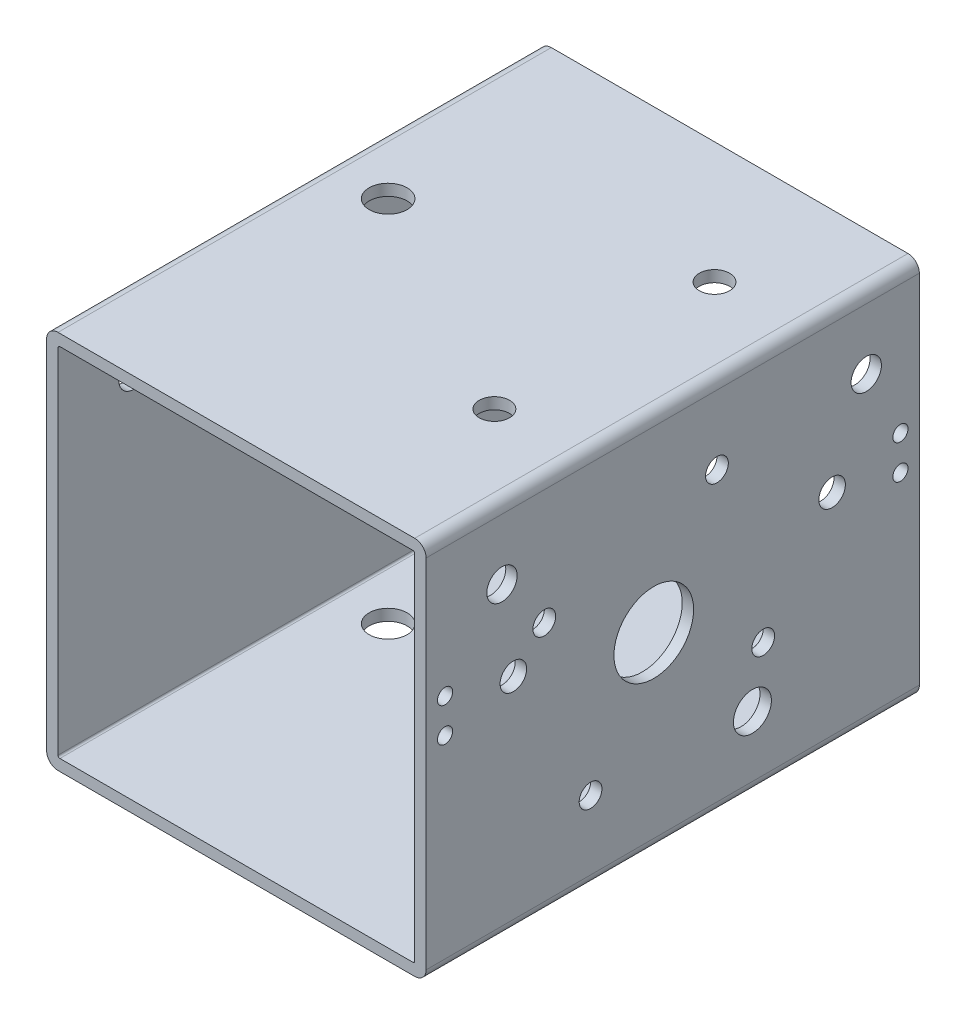
SolidWorks part; units mm, degrees
ref_plane "Front Plane" through (0, 0, 0) normal (0, 0, 1) x (1, 0, 0)
ref_plane "Top Plane" through (0, 0, 0) normal (0, 1, 0) x (1, 0, 0)
ref_plane "Right Plane" through (0, 0, 0) normal (1, 0, 0) x (0, 0, -1)
sketch "Sketch1" plane through (0, 0, 0) normal (0, 0, 1) x (1, 0, 0)
  line L1 (-50, 50) -> (50, 50)
  line L2 (-50, 50) -> (-50, -50)
  line L3 (-50, -50) -> (50, -50)
  line L4 (50, 50) -> (50, -50)
  line L5 (-50, 50) -> (50, -50) construction
  line L6 (-50, -50) -> (50, 50) construction
  point P0 (0, 0)
  dimension "D1" = 100
  dimension "D2" = 100
extrude "Extrude-Thin1" add sketch "Sketch1" along normal blind 130 thin thin type one direction reverse wall 3
fillet "Fillet1" radius 0.5 4 edges at (-47, -47, 65) (-47, 47, 65) (47, 47, 65) (47, -47, 65)
fillet "Fillet2" radius 3 4 edges at (50, -50, 65) (-50, -50, 65) (50, 50, 65) (-50, 50, 65)
sketch "Holes - top" plane through (0, 0, 0) normal (0, 1, 0) x (1, 0, 0)
  line L0 (-3, 0) -> (-3, -130) construction
  line L1 (47, -130) -> (-47, -130) construction
  line L2 (-23, 0) -> (-23, -130) construction
  line L3 (47, 0) -> (-47, 0) construction
  line L4 (17, 0) -> (17, -130) construction
  circle A0 centre (-34, -56) radius 11 construction
  circle A1 centre (28, -90) radius 11 construction
  circle A2 centre (28, -32) radius 11 construction
  dimension "D4" = 22
  dimension "D1" = 40
  dimension "D2" = 40
  dimension "D3" = 32
  dimension "D5" = 56
  dimension "D6" = 3
hole_wizard "Ø8.0 (8) Diameter Hole2" positions "Sketch6" profile "Sketch5" hole size "Ø8.0" standard "ANSI Metric" end condition through all
sketch "Sketch6" plane through (0, 50, 0) normal (0, 1, 0) x (1, 0, 0)
  point P0 (28, -32)
  point P6 (28, -90)
sketch "Sketch5" plane through (28, 50, 32) normal (1, 0, 0) x (0, 0, 1)
  line L0 (0, 0) -> (0, 100)
  line L1 (0, 100) -> (4, 100)
  line L2 (4, 100) -> (4, 0)
  line L5 (4, 0) -> (0, 0)
  line L11 (0, -6.35) -> (0, 107.95) construction
  dimension "Thru Hole Dia." = 8
  dimension "Thru Hole Depth" = 100
sketch "Holes - side" plane through (0, 0, 0) normal (1, 0, 0) x (0, 0, -1)
  line L0 (0, 0) -> (-130, 0) construction
  line L1 (-130, -47) -> (-130, 47) construction
  line L2 (-130, 20) -> (0, 20) construction
  line L3 (0, -47) -> (0, 47) construction
  line L4 (-130, -20) -> (0, -20) construction
  circle A0 centre (-110, 31) radius 11 construction
  circle A1 centre (-14, 31) radius 11 construction
  circle A2 centre (-44, -31) radius 11 construction
  dimension "D1" = 40
  dimension "D2" = 22
  dimension "D3" = 20
  dimension "D4" = 14
  dimension "D5" = 44
hole_wizard "Ø8.0 (8) Diameter Hole3" positions "Sketch9" profile "Sketch8" hole size "Ø8.0" standard "ANSI Metric" end condition through all
sketch "Sketch9" plane through (50, 0, 0) normal (1, 0, 0) x (0, 0, -1)
  point P0 (-14, 31)
  point P3 (-110, 31)
sketch "Sketch8" plane through (50, 31, 14) normal (0, 1, 0) x (0, 0, -1)
  line L0 (0, 0) -> (0, 100)
  line L1 (0, 100) -> (4, 100)
  line L2 (4, 100) -> (4, 0)
  line L5 (4, 0) -> (0, 0)
  line L11 (0, -6.35) -> (0, 107.95) construction
  dimension "Thru Hole Dia." = 8
  dimension "Thru Hole Depth" = 100
hole_wizard "Ø10.0 (10) Diameter Hole1" positions "Sketch12" profile "Sketch11" hole size "Ø10.0" standard "ANSI Metric" end condition through all
sketch "Sketch12" plane through (0, 50, 0) normal (0, 1, 0) x (1, 0, 0)
  point P0 (-34, -56)
sketch "Sketch11" plane through (-34, 50, 56) normal (1, 0, 0) x (0, 0, 1)
  line L0 (0, 0) -> (0, 100)
  line L1 (0, 100) -> (5, 100)
  line L2 (5, 100) -> (5, 0)
  line L5 (5, 0) -> (0, 0)
  line L11 (0, -6.35) -> (0, 107.95) construction
  dimension "Thru Hole Dia." = 10
  dimension "Thru Hole Depth" = 100
hole_wizard "Ø10.0 (10) Diameter Hole2" positions "Sketch14" profile "Sketch13" hole size "Ø10.0" standard "ANSI Metric" end condition through all
sketch "Sketch14" plane through (50, 0, 0) normal (1, 0, 0) x (0, 0, -1)
  point P0 (-44, -31)
sketch "Sketch13" plane through (50, -31, 44) normal (0, 1, 0) x (0, 0, -1)
  line L0 (0, 0) -> (0, 100)
  line L1 (0, 100) -> (5, 100)
  line L2 (5, 100) -> (5, 0)
  line L5 (5, 0) -> (0, 0)
  line L11 (0, -6.35) -> (0, 107.95) construction
  dimension "Thru Hole Dia." = 10
  dimension "Thru Hole Depth" = 100
hole_wizard "M8x1.25 Tapped Hole1" positions "Sketch18" profile "Sketch17" tap size "M8x1.25" standard "ANSI Metric" end condition up to next
sketch "Sketch18" plane through (-50, 0, 0) normal (-1, 0, 0) x (0, 0, 1)
  line L0 (56, 35) -> (56, -15) construction
  point P0 (56, -15)
  point P2 (56, 35)
  dimension "D1" = 56
  dimension "D2" = 35
  dimension "D3" = 15
sketch "Sketch17" plane through (-50, -15, 56) normal (0, 1, 0) x (0, 0, 1)
  line L0 (0, 0) -> (0, 3)
  line L1 (0, 3) -> (3.4, 3)
  line L2 (3.4, 3) -> (3.4, 0)
  line L5 (3.4, 0) -> (0, 0)
  line L11 (0, -6.35) -> (0, 107.95) construction
  dimension "Thru Tap Drill Dia." = 6.8
  dimension "Thru Tap Drill Depth" = 3
cosmetic thread "Hole Thread1" parameters "D2"=8
cosmetic thread "Hole Thread2" parameters "D2"=8
hole_wizard "M8x1.25 Tapped Hole2" positions "Sketch21" profile "Sketch20" tap size "M8x1.25" standard "ANSI Metric" end condition up to next
sketch "Sketch21" plane through (0, -50, 0) normal (0, -1, 0) x (-1, 0, 0)
  line L0 (20, -44) -> (-35, -44) construction
  point P0 (20, -44)
  point P2 (-35, -44)
  dimension "D1" = 44
  dimension "D2" = 35
  dimension "D3" = 20
sketch "Sketch20" plane through (-20, -50, 44) normal (1, 0, 0) x (0, 0, -1)
  line L0 (0, 0) -> (0, 3)
  line L1 (0, 3) -> (3.4, 3)
  line L2 (3.4, 3) -> (3.4, 0)
  line L5 (3.4, 0) -> (0, 0)
  line L11 (0, -6.35) -> (0, 107.95) construction
  dimension "Thru Tap Drill Dia." = 6.8
  dimension "Thru Tap Drill Depth" = 3
cosmetic thread "Hole Thread3" parameters "D2"=8
cosmetic thread "Hole Thread4" parameters "D2"=8
sketch "Holes - Nema 23 motor" plane through (0, 0, 0) normal (1, 0, 0) x (0, 0, -1)
  line L0 (-98.8427, 16.6524) -> (-53.3476, 28.8427) construction
  line L1 (-98.8427, 16.6524) -> (-86.6524, -28.8427) construction
  line L2 (-53.3476, 28.8427) -> (-41.1573, -16.6524) construction
  line L3 (-86.6524, -28.8427) -> (-41.1573, -16.6524) construction
  line L4 (-98.8427, 16.6524) -> (-41.1573, -16.6524) construction
  line L5 (-53.3476, 28.8427) -> (-86.6524, -28.8427) construction
  line L6 (0, 0) -> (-130, 0) construction
  point P1 (-70, 0)
  dimension "D1" = 70
  dimension "D2" = 47.1
  dimension "D3" = 47.1
  dimension "D4" = 15
hole_wizard "Ø21.0 (21) Diameter Hole1" positions "Sketch24" profile "Sketch23" hole size "Ø21.0" standard "ANSI Metric" end condition up to next
sketch "Sketch24" plane through (50, 0, 0) normal (1, 0, 0) x (0, 0, -1)
  point P0 (-70, 0)
sketch "Sketch23" plane through (50, 0, 70) normal (0, 1, 0) x (0, 0, -1)
  line L0 (0, 0) -> (0, 3)
  line L1 (0, 3) -> (10.5, 3)
  line L2 (10.5, 3) -> (10.5, 0)
  line L5 (10.5, 0) -> (0, 0)
  line L11 (0, -6.35) -> (0, 107.95) construction
  dimension "Thru Hole Dia." = 21
  dimension "Thru Hole Depth" = 3
hole_wizard "Ø6.0 (6) Diameter Hole1" positions "Sketch26" profile "Sketch25" hole size "Ø6.0" standard "ANSI Metric" end condition up to next
sketch "Sketch26" plane through (50, 0, 0) normal (1, 0, 0) x (0, 0, -1)
  point P0 (-41.1573, -16.6524)
  point P3 (-53.3476, 28.8427)
  point P6 (-98.8427, 16.6524)
  point P9 (-86.6524, -28.8427)
sketch "Sketch25" plane through (50, -16.6524, 41.1573) normal (0, 1, 0) x (0, 0, -1)
  line L0 (0, 0) -> (0, 3)
  line L1 (0, 3) -> (3, 3)
  line L2 (3, 3) -> (3, 0)
  line L5 (3, 0) -> (0, 0)
  line L11 (0, -6.35) -> (0, 107.95) construction
  dimension "Thru Hole Dia." = 6
  dimension "Thru Hole Depth" = 3
sketch "Sketch27" plane through (50, 0, 0) normal (1, 0, 0) x (0, 0, -1)
  line L1 (0, -47) -> (0, 47) construction
  line L2 (-130, 50) -> (0, 50) construction
  line L3 (-65, 66.9997) -> (-65, -40.3101) construction
  line L4 (-130, -47) -> (-130, 47) construction
  circle A0 centre (-5, 13) radius 2
  circle A1 centre (-5, 4) radius 2
  circle A2 centre (-23, 8.5) radius 3.5
  circle A3 centre (-107, 8.5) radius 3.5
  circle A4 centre (-125, 4) radius 2
  circle A5 centre (-125, 13) radius 2
  dimension "D1" = 4
  dimension "D2" = 9
  dimension "D3" = 5
  dimension "D4" = 46
  dimension "D7" = 18
  dimension "D8" = 4.5
  dimension "D9" = 7
  dimension "D5" = 0
  dimension "D6" = 65
extrude "Cut-Extrude1" cut sketch "Sketch27" against normal up to next
equation "\"a\"= \"Trolley Profile@Plasma Beta.Assembly\""
equation "\"b\"= \"Trolley Profile Thickness@Plasma Beta.Assembly\""
equation "\"L\"= 130"
equation "\"D2@Sketch1\"=\"a\""
equation "\"D1@Sketch1\"=\"a\""
equation "\"D1@Extrude-Thin1\"=\"L\""
equation "\"D5@Extrude-Thin1\"=\"b\""
equation "\"D1@Fillet2\"=\"b\""
equation "\"d-bearing\"= 22'diameter of bearing"
equation "\"a-small\"= \"Beam Profile@Plasma Beta.Assembly\"'profile of smaller beam"
equation "\"D4@Holes - top\"=\"d-bearing\""
equation "\"D2@Holes - side\"=\"d-bearing\""
equation "\"D1@Holes - top\"=\"a-small\""
equation "\"D1@Holes - side\"=\"a-small\""
